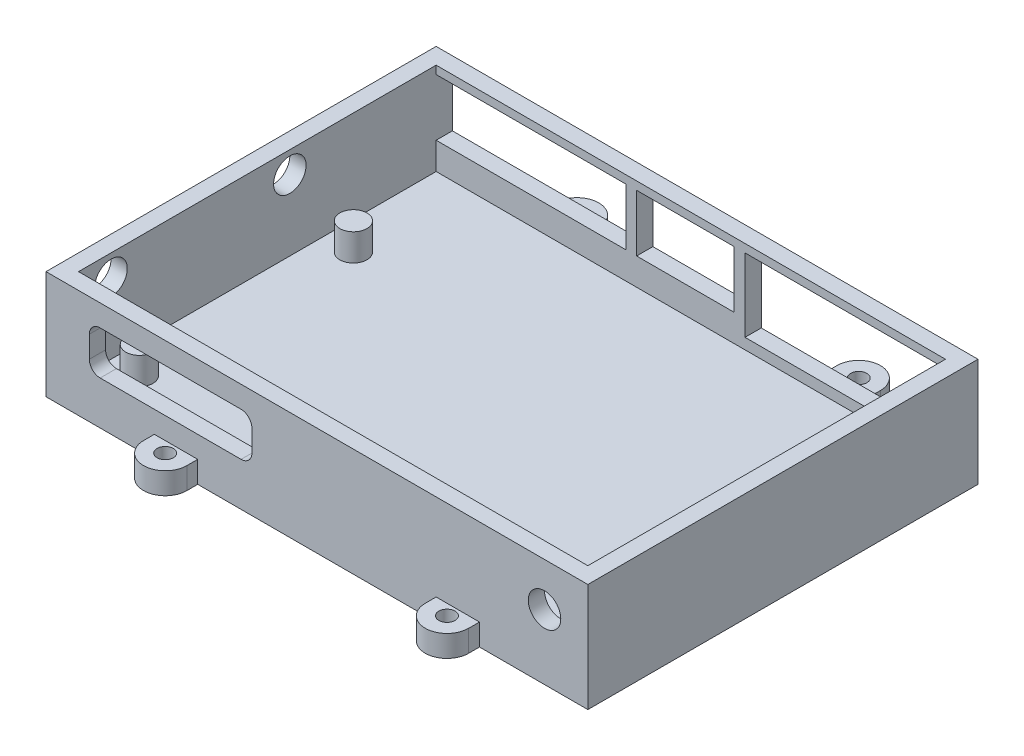
SolidWorks part; units mm, degrees
ref_plane "Front" through (0, 0, 0) normal (0, 0, 1) x (1, 0, 0)
ref_plane "Top" through (0, 0, 0) normal (0, 1, 0) x (1, 0, 0)
ref_plane "Right" through (0, 0, 0) normal (1, 0, 0) x (0, 0, -1)
sketch "plate" plane through (0, 0, 0) normal (0, 1, 0) x (1, 0, 0)
  line L1 (-49.1968, 43.2851) -> (50.8032, 43.2851)
  line L2 (-49.1968, 43.2851) -> (-49.1968, -28.7149)
  line L3 (-49.1968, -28.7149) -> (50.8032, -28.7149)
  line L4 (50.8032, 43.2851) -> (50.8032, -28.7149)
  dimension "D1" = 100
  dimension "D2" = 72
extrude "Boss-Extrude1" add sketch "plate" along normal blind 20
sketch "wall" plane through (0, 20, 0) normal (0, 1, 0) x (1, 0, 0)
  line L0 (50.8032, 43.2851) -> (-49.1968, 43.2851) construction
  line L1 (-46.1968, 40.2851) -> (47.8032, 40.2851)
  line L2 (-46.1968, 40.2851) -> (-46.1968, -25.7149)
  line L3 (-46.1968, -25.7149) -> (47.8032, -25.7149)
  line L4 (47.8032, 40.2851) -> (47.8032, -25.7149)
  line L5 (-49.1968, 43.2851) -> (-49.1968, -28.7149) construction
  line L6 (-49.1968, -28.7149) -> (50.8032, -28.7149) construction
  line L7 (50.8032, -28.7149) -> (50.8032, 43.2851) construction
  dimension "D1" = 3
  dimension "D2" = 3
  dimension "D3" = 3
  dimension "D4" = 3
extrude "Cut-Extrude1" cut sketch "wall" against normal blind 17
sketch "mount_column" plane through (0, 3, 0) normal (0, 1, 0) x (1, 0, 0)
  line L0 (-46.1968, -25.7149) -> (47.8032, -25.7149) construction
  line L1 (-46.1968, -25.7149) -> (47.8032, -25.7149) construction
  line L2 (47.8032, 40.2851) -> (-46.1968, 40.2851) construction
  circle A0 centre (-40.9628, -19.7149) radius 2.5
  circle A1 centre (-40.9628, 19.7851) radius 2.5
  circle A2 centre (43.0372, -17.7149) radius 2.5
  circle A3 centre (43.0372, 19.7851) radius 2.5
  dimension "D1" = 5
  dimension "D3" = 5
  dimension "D4" = 5
  dimension "D9" = 5
  dimension "D2" = 6
  dimension "D5" = 8
  dimension "D6" = 84
  dimension "D7" = 39.5
  dimension "D8" = 20.5
  dimension "D10" = 84
  dimension "D11" = 37.5
extrude "Boss-Extrude2" add sketch "mount_column" along normal blind 5
sketch "back_sockets" plane through (0, 0, -43.2851) normal (0, 0, -1) x (-1, 0, 0)
  line L1 (-47.8032, 18.5) -> (-10.8032, 18.5)
  line L2 (-47.8032, 18.5) -> (-47.8032, 5)
  line L3 (-47.8032, 5) -> (-10.8032, 5)
  line L4 (-10.8032, 18.5) -> (-10.8032, 5)
  line L19 (11.1968, 18.5) -> (46.1968, 18.5)
  line L20 (11.1968, 18.5) -> (11.1968, 8)
  line L21 (11.1968, 8) -> (46.1968, 8)
  line L22 (46.1968, 18.5) -> (46.1968, 8)
  line L23 (-8.8032, 18.5) -> (9.1968, 18.5)
  line L24 (-8.8032, 18.5) -> (-8.8032, 8)
  line L25 (-8.8032, 8) -> (9.1968, 8)
  line L26 (9.1968, 18.5) -> (9.1968, 8)
  line L31 (-50.8032, 20) -> (-50.8032, 0) construction
  line L32 (-50.8032, 20) -> (49.1968, 20) construction
  line L33 (-50.8032, 0) -> (49.1968, 0) construction
  point P4 (0, 0)
  point P9 (0, 0)
  point P10 (0, 0)
  point P19 (0, 0)
  dimension "D1" = 3
  dimension "D2" = 40
  dimension "D3" = 42
  dimension "D4" = 60
  dimension "D5" = 62
  dimension "D6" = 97
  dimension "D9" = 1.5
  dimension "D10" = 5
extrude "Cut-Extrude2" cut sketch "back_sockets" against normal blind 18
sketch "usb type-c" plane through (0, 0, 28.7149) normal (0, 0, 1) x (1, 0, 0)
  line L0 (-49.1968, 20) -> (-49.1968, 0) construction
  line L1 (-39.1968, 16) -> (-13.1968, 16)
  line L2 (-41.1968, 14) -> (-41.1968, 10)
  line L3 (-39.1968, 8) -> (-13.1968, 8)
  line L4 (-11.1968, 14) -> (-11.1968, 10)
  line L5 (-49.1968, 20) -> (50.8032, 20) construction
  arc A0 (-13.1968, 8) -> (-11.1968, 10) centre (-13.1968, 10) ccw
  arc A1 (-13.1968, 16) -> (-11.1968, 14) centre (-13.1968, 14) cw
  arc A2 (-41.1968, 10) -> (-39.1968, 8) centre (-39.1968, 10) ccw
  arc A3 (-39.1968, 16) -> (-41.1968, 14) centre (-39.1968, 14) ccw
  point P4 (-41.1968, 12)
  point P7 (-11.1968, 12)
  point P8 (-26.1968, 8)
  point P11 (-26.1968, 16)
  dimension "D5" = 2
  dimension "D1" = 8
  dimension "D2" = 38
  dimension "D3" = 12
  dimension "D4" = 4
extrude "Cut-Extrude4" cut sketch "usb type-c" against normal blind 18
sketch "ant1-hole" plane through (-49.1968, 0, 0) normal (-1, 0, 0) x (0, 0, 1)
  line L2 (-43.2851, 20) -> (28.7149, 20) construction
  line L3 (-43.2851, 20) -> (-43.2851, 0) construction
  circle A0 centre (-13.2851, 16) radius 3
  dimension "D1" = 4
  dimension "D2" = 30
sketch "ant2-hole" plane through (-49.1968, 0, 0) normal (-1, 0, 0) x (0, 0, 1)
  line L0 (-43.2851, 20) -> (28.7149, 20) construction
  line L1 (28.7149, 20) -> (28.7149, 0) construction
  circle A0 centre (19.7149, 16) radius 3
  dimension "D1" = 4
  dimension "D2" = 9
extrude "Cut-Extrude5" cut sketch "ant1-hole" against normal blind 10
extrude "Cut-Extrude6" cut sketch "ant2-hole" against normal blind 10
sketch "reset-hole" plane through (0, 0, 28.7149) normal (0, 0, 1) x (1, 0, 0)
  line L1 (50.8032, 20) -> (50.8032, 0) construction
  line L2 (-49.1968, 20) -> (50.8032, 20) construction
  circle A0 centre (42.8032, 12) radius 3
  dimension "D1" = 8
  dimension "D2" = 8
extrude "Cut-Extrude8" cut sketch "reset-hole" against normal blind 6
sketch "lug1" plane through (0, 0, 0) normal (0, 1, 0) x (1, 0, 0)
  line L0 (-29.1968, -28.7149) -> (-29.1968, -30.7149)
  line L1 (-49.1968, -28.7149) -> (50.8032, -28.7149) construction
  line L2 (-21.1968, -28.7149) -> (-29.1968, -28.7149)
  line L3 (-21.1968, -28.7149) -> (-21.1968, -30.7149)
  line L4 (-49.1968, 43.2851) -> (-49.1968, -28.7149) construction
  arc A0 (-29.1968, -30.7149) -> (-21.1968, -30.7149) centre (-25.1968, -30.7149) ccw
  circle A1 centre (-25.1968, -30.7149) radius 1.5
  point P6 (-29.1968, -29.7149)
  dimension "D1" = 8
  dimension "D2" = 2
  dimension "D3" = 20
extrude "Boss-Extrude10" add sketch "lug1" along normal blind 4
sketch "lug2" plane through (0, 0, 0) normal (0, 1, 0) x (1, 0, 0)
  line L0 (22.8032, -28.7149) -> (22.8032, -30.7149)
  line L2 (30.8032, -28.7149) -> (22.8032, -28.7149)
  line L3 (30.8032, -28.7149) -> (30.8032, -30.7149)
  arc A0 (22.8032, -30.7149) -> (30.8032, -30.7149) centre (26.8032, -30.7149) ccw
  circle A1 centre (26.8032, -30.7149) radius 1.5
  dimension "D1" = 8
  dimension "D2" = 2
  dimension "D3" = 20
extrude "Boss-Extrude11" add sketch "lug2" along normal blind 4
sketch "lug3" plane through (0, 0, 0) normal (0, 1, 0) x (1, 0, 0)
  line L0 (30.8032, 43.2709) -> (30.8032, 45.2709)
  line L1 (22.8032, 43.2709) -> (30.8032, 43.2709)
  line L2 (22.8032, 43.2709) -> (22.8032, 45.2709)
  arc A0 (30.8032, 45.2709) -> (22.8032, 45.2709) centre (26.8032, 45.2709) ccw
  circle A1 centre (26.8032, 45.2709) radius 1.5
  dimension "D1" = 20
sketch "lug4" plane through (0, 0, 0) normal (0, 1, 0) x (1, 0, 0)
  line L0 (-21.1968, 43.2851) -> (-21.1968, 45.2851)
  line L1 (-29.1968, 43.2851) -> (-21.1968, 43.2851)
  line L2 (-29.1968, 43.2851) -> (-29.1968, 45.2851)
  arc A0 (-21.1968, 45.2851) -> (-29.1968, 45.2851) centre (-25.1968, 45.2851) ccw
  circle A1 centre (-25.1968, 45.2851) radius 1.5
  dimension "D1" = 20
extrude "Boss-Extrude12" add sketch "lug3" along normal blind 4
extrude "Boss-Extrude13" add sketch "lug4" along normal blind 4
